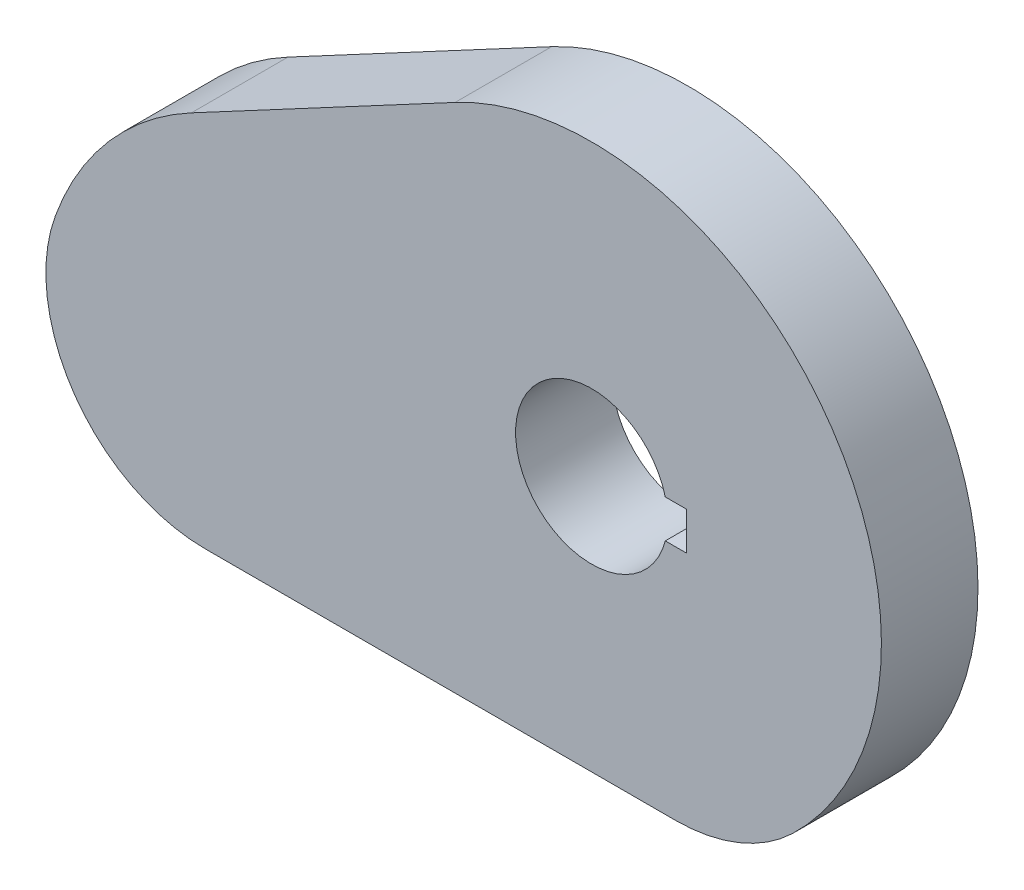
SolidWorks part; units mm, degrees
ref_plane "Front" through (0, 0, 0) normal (0, 0, 1) x (1, 0, 0)
ref_plane "Top" through (0, 0, 0) normal (0, 1, 0) x (1, 0, 0)
ref_plane "Right" through (0, 0, 0) normal (1, 0, 0) x (0, 0, -1)
other "Configuration Table"
ref_axis "Axis1" through (0, 0, -80.9) along (0, 0, 1)
sketch "Sketch1" plane through (0, 0, 0) normal (0, 0, 1) x (1, 0, 0)
  line L0 (-105.2567, 30.1594) -> (-35.9069, 67.2096)
  line L1 (-101.6, -67.31) -> (22.0337, -67.31)
  line L2 (19.3649, 5) -> (25, 5)
  line L4 (19.3649, -5) -> (25, -5)
  line L5 (25, 5) -> (25, -5)
  arc A0 (22.0337, -67.31) -> (52.8808, -54.864) centre (22.0337, -22.86) ccw
  arc A1 (-141.0169, -11.1608) -> (-101.6, -67.31) centre (-101.6, -25.4) ccw
  arc A2 (-105.2567, 30.1594) -> (-141.0169, -11.1608) centre (-69.3498, -37.0503) ccw
  arc A3 (-26.9632, 71.2701) -> (52.8808, -54.864) centre (0, 0) cw
  arc A4 (19.3649, 5) -> (19.3649, -5) centre (0, 0) ccw
  arc A5 (-35.9069, 67.2096) -> (-26.9632, 71.2701) centre (0, 0) cw
  point P5 (25, 0)
  dimension "D1" = 44.45
  dimension "D3" = 76.2
  dimension "D4" = 76.2
  dimension "D5" = 41.91
  dimension "D7" = 40
  dimension "D2" = 101.6
  dimension "D6" = 25.4
  dimension "D8" = 25
  dimension "D9" = 10
extrude "Extrude1" add sketch "Sketch1" along normal mid plane 25.4
